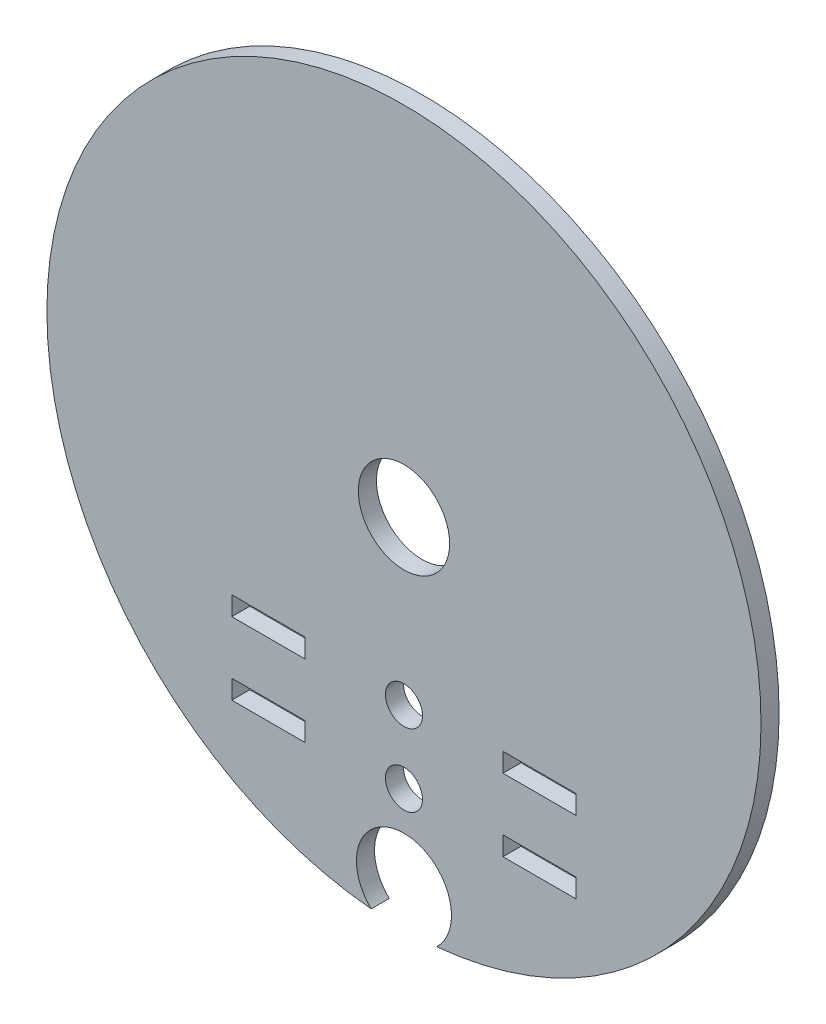
SolidWorks part; units mm, degrees
ref_plane "前视基准面" through (0, 0, 0) normal (0, 0, 1) x (1, 0, 0)
ref_plane "上视基准面" through (0, 0, 0) normal (0, 1, 0) x (1, 0, 0)
ref_plane "右视基准面" through (0, 0, 0) normal (1, 0, 0) x (0, 0, -1)
sketch "草图1" plane through (0, 0, 0) normal (0, 0, 1) x (1, 0, 0)
  line L0 (0, 0) -> (0, 8) construction
  line L1 (0, 8) -> (-15, 8) construction
  line L2 (0, 4) -> (-3.9018, 4) construction
  line L3 (-19.05, 9.05) -> (-10.95, 9.05)
  line L4 (-19.05, 9.05) -> (-19.05, 6.95)
  line L5 (-19.05, 6.95) -> (-10.95, 6.95)
  line L6 (-10.95, 9.05) -> (-10.95, 6.95)
  line L7 (-19.05, 9.05) -> (-10.95, 6.95) construction
  line L8 (-19.05, 6.95) -> (-10.95, 9.05) construction
  line L9 (-10.95, -1.05) -> (-10.95, 1.05)
  line L10 (-19.05, -1.05) -> (-10.95, -1.05)
  line L11 (-19.05, -1.05) -> (-19.05, 1.05)
  line L12 (-19.05, 1.05) -> (-10.95, 1.05)
  line L13 (10.95, 9.05) -> (10.95, 6.95)
  line L14 (19.05, 9.05) -> (10.95, 9.05)
  line L15 (19.05, 9.05) -> (19.05, 6.95)
  line L16 (19.05, 6.95) -> (10.95, 6.95)
  line L17 (19.05, 1.05) -> (10.95, 1.05)
  line L18 (19.05, -1.05) -> (19.05, 1.05)
  line L19 (19.05, -1.05) -> (10.95, -1.05)
  line L20 (10.95, -1.05) -> (10.95, 1.05)
  circle A0 centre (0, 0) radius 2.05
  circle A1 centre (0, 8) radius 2.05
  circle A2 centre (0, 26) radius 5.05
  circle A4 centre (0, 26) radius 12 construction
  circle A6 centre (0, 26) radius 39.5 construction
  circle A9 centre (0, -8.5) radius 2.05 construction
  circle A10 centre (0, -13.5) radius 3.6241 construction
  arc A11 (-3.6245, -13.3334) -> (3.6203, -13.3337) centre (-0.0019, -9.5259) cw
  arc A12 (-3.6245, -13.3334) -> (3.6203, -13.3337) centre (0, 26) cw
  dimension "D1" = 4.1
  dimension "D3" = 4.1
  dimension "D7" = 10.1
  dimension "D9" = 24
  dimension "D10" = 79
  dimension "D11" = 8.5
  dimension "D2" = 8
  dimension "D4" = 15
  dimension "D5" = 8.1
  dimension "D6" = 2.1
  dimension "D8" = 18
extrude "凸台-拉伸1" add sketch "草图1" along normal blind 2
